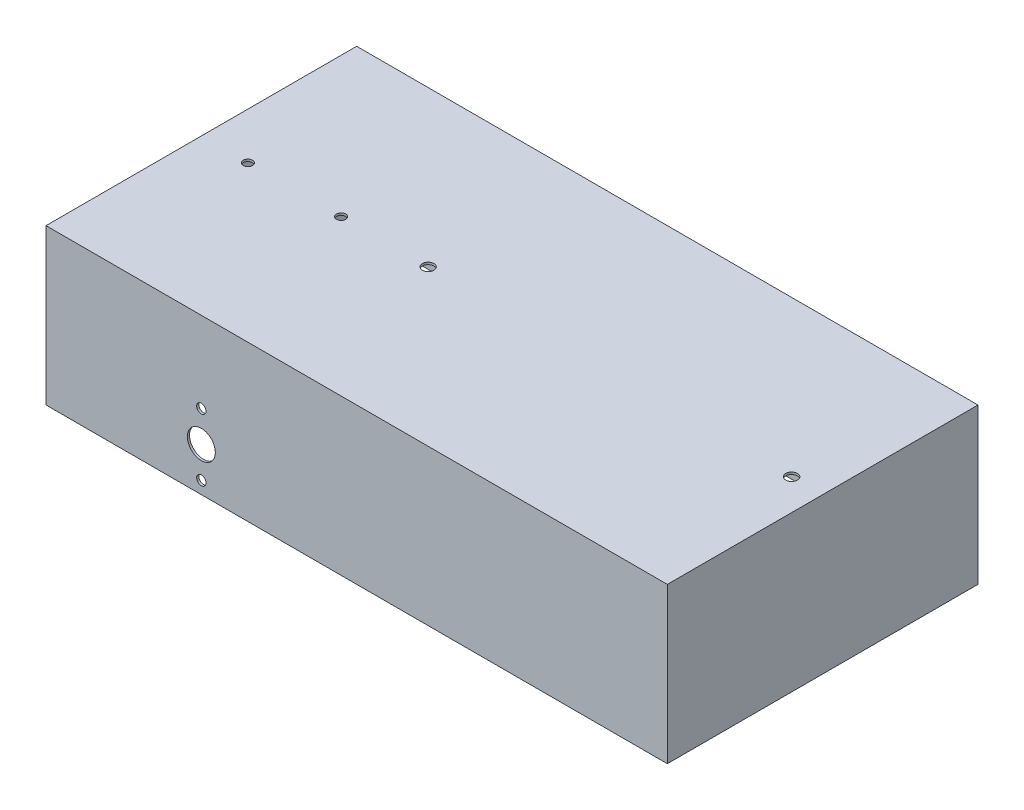
SolidWorks part; units mm, degrees
ref_plane "Front Plane" through (0, 0, 0) normal (0, 0, 1) x (1, 0, 0)
ref_plane "Top Plane" through (0, 0, 0) normal (0, 1, 0) x (1, 0, 0)
ref_plane "Right Plane" through (0, 0, 0) normal (1, 0, 0) x (0, 0, -1)
sketch "Sketch1" plane through (0, 0, 0) normal (0, 1, 0) x (1, 0, 0)
  line L1 (0, 50) -> (200, 50)
  line L2 (0, 50) -> (0, -50)
  line L3 (0, -50) -> (200, -50)
  line L4 (200, 50) -> (200, -50)
  point P4 (0, 0)
  dimension "D1" = 200
  dimension "D2" = 100
extrude "Boss-Extrude1" add sketch "Sketch1" along normal blind 50
sketch "Sketch2" plane through (0, 0, 50) normal (0, 0, 1) x (1, 0, 0)
  line L0 (0, 50) -> (0, 0) construction
  line L1 (50, 24) -> (50, 4) construction
  line L2 (0, 50) -> (200, 50) construction
  circle A0 centre (50, 14) radius 4.5
  circle A1 centre (50, 4) radius 1.5
  circle A2 centre (50, 24) radius 1.5
  point P0 (50, 14)
  point P9 (50, 14)
  dimension "D3" = 9
  dimension "D4" = 3
  dimension "D1" = 50
  dimension "D2" = 36
  dimension "D5" = 20
sketch "Sketch3" plane through (0, 0, 0) normal (0, -1, 0) x (1, 0, 0)
  line L0 (0.7, 49.3) -> (0.7, -49.3)
  line L1 (0.7, -49.3) -> (199.3, -49.3)
  line L2 (199.3, -49.3) -> (199.3, 49.3)
  line L3 (199.3, 49.3) -> (0.7, 49.3)
  line L4 (0, 50) -> (0, -50)
  line L5 (0, -50) -> (200, -50)
  line L6 (200, -50) -> (200, 50)
  line L7 (200, 50) -> (0, 50)
  line L8 (0, 50) -> (0, -50) construction
  line L9 (0, -50) -> (200, -50) construction
  line L10 (200, -50) -> (200, 50) construction
  line L11 (200, 50) -> (0, 50) construction
  dimension "D1" = 0
  dimension "D2" = 0.7
extrude "Cut-Extrude1" cut sketch "Sketch3" against normal offset from surface (49.3 mm away) 0.7 up to face at (100, 50, 0)
sketch "Sketch4" plane through (0, 0, 0) normal (0, -1, 0) x (1, 0, 0)
  line L0 (0.7, -49.3) -> (199.3, -49.3) construction
  line L1 (145, -49.3) -> (199.3, -49.3)
  line L2 (145, -49.3) -> (145, 49.3)
  line L3 (145, 49.3) -> (199.3, 49.3)
  line L4 (199.3, -49.3) -> (199.3, 49.3)
  line L5 (199.3, 49.3) -> (0.7, 49.3) construction
  line L6 (160, -47.9) -> (160, 49.3) construction
  line L7 (200, -50) -> (200, 50) construction
  line L8 (199.3, -49.3) -> (199.3, 49.3) construction
  circle A0 centre (160, 0.7) radius 11.43 construction
  point P12 (160, 0.7)
  dimension "D3" = 22.86
  dimension "D1" = 40
  dimension "D2" = 55
  dimension "D4" = 50
extrude "Boss-Extrude2" add sketch "Sketch4" against normal blind 0.7
extrude "Cut-Extrude2" cut sketch "Sketch2" against normal through all
sketch "Sketch6" plane through (0, 0, 50) normal (0, 0, 1) x (1, 0, 0)
  line L0 (4.6, 50) -> (4.6, 0) construction
  line L1 (0, 50) -> (200, 50) construction
  line L2 (200, 0) -> (0, 0) construction
  line L3 (0, 45) -> (200, 45) construction
  line L4 (0, 50) -> (0, 0) construction
  line L5 (200, 50) -> (200, 0) construction
  line L6 (0, 35) -> (200, 35) construction
  line L7 (54.1, 45) -> (54.1, 35) construction
  line L8 (69.1, 45) -> (69.1, 35) construction
  circle A0 centre (4.6, 45) radius 1.5
  circle A1 centre (4.6, 35) radius 1.5
  circle A2 centre (54.1, 45) radius 1.5
  circle A3 centre (54.1, 35) radius 1.5
  circle A4 centre (69.1, 45) radius 1.5
  circle A5 centre (69.1, 35) radius 1.5
  dimension "D1" = 3
  dimension "D3" = 5
  dimension "D4" = 10
  dimension "D5" = 4.6
  dimension "D6" = 15
  dimension "D7" = 54.1
extrude "Cut-Extrude3" [suppressed] cut sketch "Sketch6" against normal up to surface (0.7 mm away) up to face at (51.5, 4, 49.3)
sketch "Sketch7" plane through (0, 0, 0) normal (-1, 0, 0) x (0, 0, 1)
  line L0 (42, 50) -> (42, 0) construction
  line L1 (-50, 50) -> (50, 50) construction
  line L2 (-50, 0) -> (50, 0) construction
  circle A0 centre (42, 45) radius 1.5
  circle A1 centre (42, 35) radius 1.5
  dimension "D4" = 3
  dimension "D1" = 8
  dimension "D2" = 5
  dimension "D3" = 10
extrude "Cut-Extrude4" [suppressed] cut sketch "Sketch7" against normal up to surface (0.7 mm away) up to face at (0.7, 24.65, 0)
sketch "Sketch8" plane through (0, 0, 0) normal (0, -1, 0) x (1, 0, 0)
  line L0 (160, -47.9) -> (160, 49.3) construction
  circle A0 centre (160, 8.45) radius 1.21
  circle A1 centre (160, -7.05) radius 1.21
  dimension "D2" = 2.42
  dimension "D1" = 7.75
  dimension "D3" = 7.75
extrude "Cut-Extrude6" cut sketch "Sketch8" against normal blind 1.8 contours A1 | A0
sketch "Sketch9" plane through (0, 50, 0) normal (0, 1, 0) x (1, 0, 0)
  line L0 (0, 0) -> (200, 0) construction
  line L1 (200, 50) -> (200, -50) construction
  circle A0 centre (15, 0) radius 1.5
  circle A1 centre (45, 0) radius 1.5
  dimension "D1" = 3
  dimension "D2" = 15
  dimension "D3" = 30
sketch "Sketch10" plane through (0, 49.3, 0) normal (0, -1, 0) x (1, 0, 0)
  line L0 (0, 0) -> (200, 0)
  line L1 (200, -50) -> (200, 50) construction
  circle A0 centre (190, 0) radius 1.87
  circle A1 centre (73, 0) radius 1.87
  point P9 (0, 0)
  point P10 (0, 0)
  point P11 (191.0398, 0)
  point P12 (200, 0)
  dimension "D2" = 3.74
  dimension "D1" = 117
  dimension "D3" = 10
extrude "Cut-Extrude8" cut sketch "Sketch10" against normal up to surface (0.7 mm away) contours A0 | A1 up to face at (100, 50, 0)
extrude "Cut-Extrude7" cut sketch "Sketch9" against normal through all
